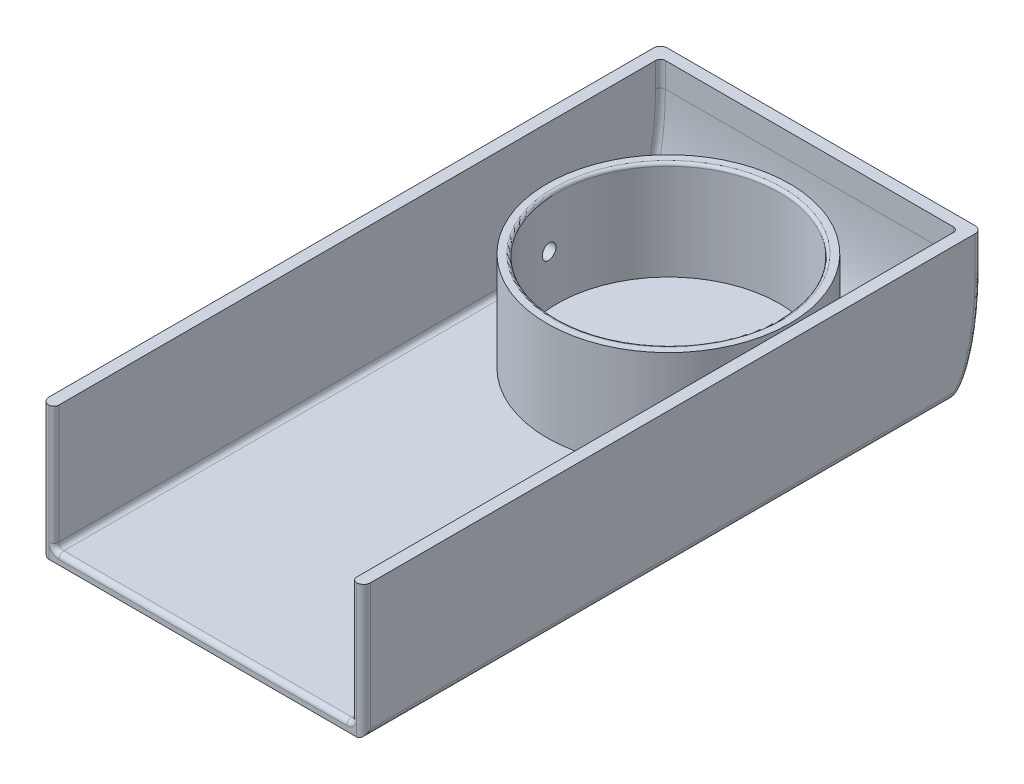
SolidWorks part; units mm, degrees
ref_plane "Front Plane" through (0, 0, 0) normal (0, 0, 1) x (1, 0, 0)
ref_plane "Top Plane" through (0, 0, 0) normal (0, 1, 0) x (1, 0, 0)
ref_plane "Right Plane" through (0, 0, 0) normal (1, 0, 0) x (0, 0, -1)
sketch "Sketch1" plane through (0, 0, 0) normal (0, 1, 0) x (1, 0, 0)
  line L1 (0, 0) -> (65, 0)
  line L2 (0, 0) -> (0, -125)
  line L3 (0, -125) -> (65, -125)
  line L4 (65, 0) -> (65, -125)
  dimension "D1" = 65
  dimension "D2" = 125
extrude "Boss-Extrude1" add sketch "Sketch1" along normal blind 2
sketch "Sketch2" plane through (0, 2, 0) normal (0, 1, 0) x (1, 0, 0)
  line L4 (2.4, -2.4) -> (2.4, -122.6)
  line L5 (2.4, -122.6) -> (62.6, -122.6)
  line L6 (62.6, -122.6) -> (62.6, -2.4)
  line L7 (62.6, -2.4) -> (2.4, -2.4)
  line L8 (0, 0) -> (0, -125)
  line L9 (0, -125) -> (65, -125)
  line L10 (65, -125) -> (65, 0)
  line L11 (65, 0) -> (0, 0)
  line L12 (0, 0) -> (0, -125)
  line L13 (0, -125) -> (65, -125)
  line L14 (65, -125) -> (65, 0)
  line L15 (65, 0) -> (0, 0)
  dimension "D1" = 0
  dimension "D2" = 2.4
extrude "Boss-Extrude2" add sketch "Sketch2" along normal blind 25
sketch "Sketch3" plane through (0, 0, 122.6) normal (0, 0, -1) x (-1, 0, 0)
  line L1 (-62.6, 27) -> (-2.4, 27)
  line L2 (-62.6, 27) -> (-62.6, 2)
  line L3 (-62.6, 2) -> (-2.4, 2)
  line L4 (-2.4, 27) -> (-2.4, 2)
extrude "Cut-Extrude1" cut sketch "Sketch3" against normal blind 25
fillet "Fillet1" radius 20 1 edges at (32.5, 2, 2.4)
fillet "Fillet2" radius 6 1 edges at (32.5, 0, 0)
fillet "Fillet3" radius 1 9 edges at (62.6, 14.5, 125) (2.4, 14.5, 125) (32.5, 2, 125)
fillet "Fillet4" radius 1.4 8 edges at (65, 13.5, 125) (0, 13.5, 125)
sketch "Sketch5" plane through (0, 2, 0) normal (0, 1, 0) x (1, 0, 0)
  line L0 (61.6, -8.4) -> (3.4, -8.4) construction
  line L1 (3.4, -124) -> (61.6, -124) construction
  circle A0 centre (32.5, -30.9) radius 22.5
  circle A1 centre (32.5, -30.9) radius 24.5
  point P6 (32.5, -124)
  dimension "D1" = 45
  dimension "D2" = 22.5
  dimension "D3" = 0
  dimension "D4" = 2
extrude "Boss-Extrude3" add sketch "Sketch5" along normal blind 20
fillet "Fillet6" radius 0.6 1 edges at (32.5, 22, 53.4)
sketch "Sketch6" plane through (2.4, 0, 0) normal (1, 0, 0) x (0, 0, -1)
  line L0 (-8.4, 2) -> (-124, 2) construction
  circle A0 centre (-32.609, 12) radius 1.5
  dimension "D2" = 3
  dimension "D1" = 10
extrude "Cut-Extrude3" cut sketch "Sketch6" along normal blind 20
